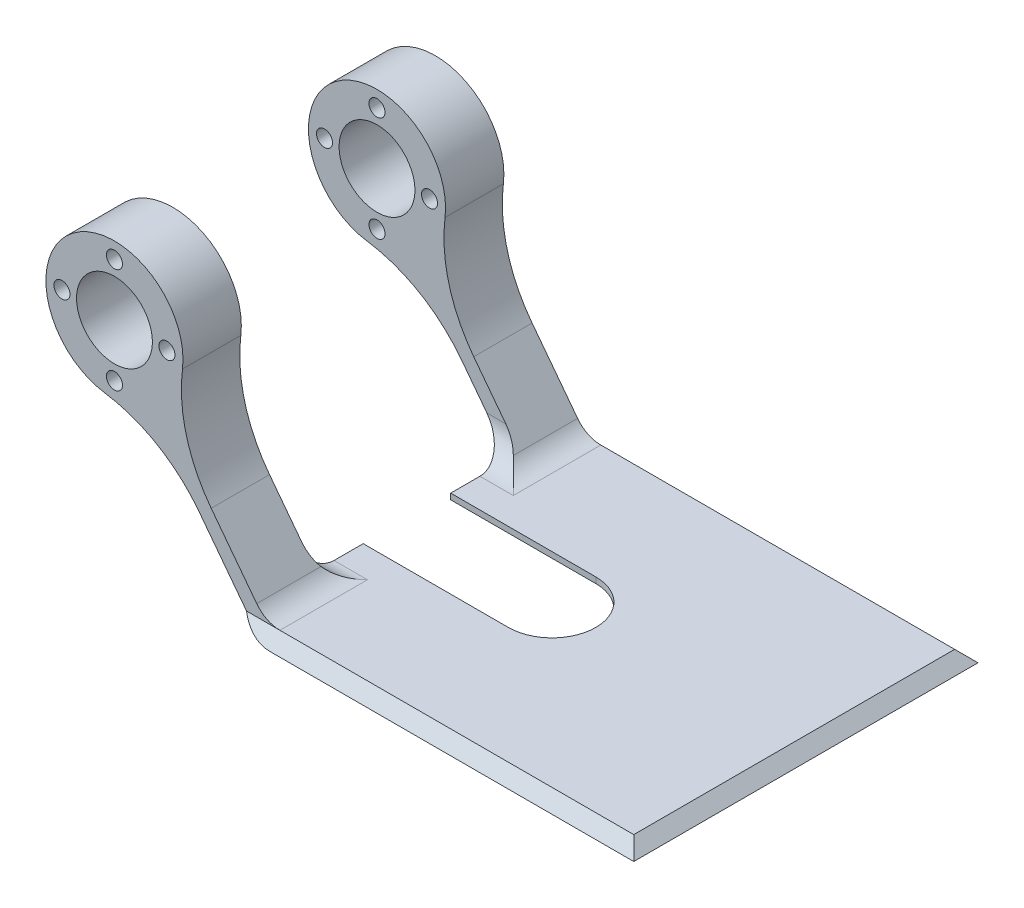
SolidWorks part; units mm, degrees
material "ABS"
ref_plane "Front Plane" through (0, 0, 0) normal (0, 0, 1) x (1, 0, 0)
ref_plane "Top Plane" through (0, 0, 0) normal (0, 1, 0) x (1, 0, 0)
ref_plane "Right Plane" through (0, 0, 0) normal (1, 0, 0) x (0, 0, -1)
sketch "Sketch1" plane through (0, 0, 0) normal (0, 1, 0) x (1, 0, 0)
  line L4 (-71.78, 65.2073) -> (70.97, 65.2073)
  line L5 (70.97, 65.2073) -> (70.97, -64.7927)
  line L6 (70.97, -64.7927) -> (-71.78, -64.7927)
  line L8 (-71.78, 65.2073) -> (-71.78, -64.7927)
  line L9 (-71.78, 65.2073) -> (70.97, -64.7927) construction
  line L10 (-71.78, -64.7927) -> (70.97, 65.2073) construction
  point P0 (-0.405, 0.2073)
  point P3 (-71.78, 0.2073)
  dimension "D1" = 142.75
  dimension "D2" = 130
extrude "Boss-Extrude1" add sketch "Sketch1" along normal blind 4
sketch "Sketch5" plane through (0, 4, 0) normal (0, 1, 0) x (1, 0, 0)
  line L1 (-116.78, 0.2073) -> (70.97, 0.2073) construction
  line L3 (70.97, -64.7927) -> (70.97, 65.2073) construction
ref_plane "Plane1" through (0, 0, -0.2073) normal (0, 0, 1) x (1, 0, 0)
chamfer "Chamfer4" distance 10 angle 45 2 edges at (-0.405, 4, -65.2073) (-0.405, 4, 64.7927)
chamfer "Chamfer5" distance 10 angle 45 1 edges at (70.97, 4, -0.2073)
ref_plane "Plane2" through (0, 0, 54.7927) normal (0, 0, -1) x (-1, 0, 0)
sketch "Sketch11" plane through (0, 0, 54.7927) normal (0, 0, -1) x (-1, 0, 0)
  line L0 (65.28, 4) -> (71.78, 4)
  line L1 (71.78, 4) -> (110.6251, 55.0273)
  line L2 (110.6251, 55.0273) -> (106.51, 58.16)
  line L3 (65.28, 4) -> (106.51, 58.16)
  line L4 (68.53, 4) -> (117.0476, 67.7331) construction
  line L5 (-60.97, 4) -> (71.78, 4) construction
  line L6 (117.0476, 67.7331) -> (99.0476, 67.7331) construction
  line L7 (117.0476, 67.7331) -> (135.0476, 67.7331) construction
  line L8 (117.0476, 67.7331) -> (117.0476, 85.7331) construction
  line L9 (117.0476, 67.7331) -> (117.0476, 49.7331) construction
  circle A0 centre (117.0476, 67.7331) radius 23.5
  circle A1 centre (99.0476, 67.7331) radius 2.75
  circle A2 centre (117.0476, 85.7331) radius 2.75
  circle A3 centre (135.0476, 67.7331) radius 2.75
  circle A4 centre (117.0476, 49.7331) radius 2.75
  circle A5 centre (117.0476, 67.7331) radius 13
  point P2 (108.5676, 56.5936)
  point P5 (54.3617, 2.4522)
  point P7 (54.3617, 2.4522)
  point P20 (71.78, 4)
  dimension "D6" = 5.5
  dimension "D9" = 26
  dimension "D10" = 47
  dimension "D1" = 6.5
  dimension "D2" = 54.16
  dimension "D3" = 41.23
  dimension "D4" = 18
  dimension "D5" = 18
  dimension "D7" = 18
  dimension "D8" = 18
  dimension "D11" = 14
extrude "Boss-Extrude3" add sketch "Sketch11" along normal blind 20 contours L4 L0 L1 A0 | L0 L4 A0 L3 | L1 A0 L3 L2 A5 A4 A3 A2 A1 | L4 A0 L1 L2 | A0 L4 L2 L3 region at (-84.3511, 26.9304, 54.7927) region at (-87.0055, 26.1466, 54.7927) region at (-108.0515, 88.7217, 54.7927) region at (-104.6785, 53.6142, 54.7927) region at (-106.7309, 52.0518, 54.7927)
sketch "Sketch12" plane through (0, 4, 0) normal (0, 1, 0) x (1, 0, 0)
  line L0 (60.97, -54.7927) -> (60.97, 55.2073) construction
  line L2 (-71.78, 55.2073) -> (-71.78, -34.7927) construction
  line L8 (-62.0334, -22.2927) -> (12.9666, -22.2927)
  line L9 (22.9666, -12.2927) -> (22.9666, 22.7073)
  line L10 (22.9666, 22.7073) -> (-62.0334, 22.7073)
  line L11 (-71.78, 15.2073) -> (-71.78, -14.7927)
  line L12 (60.97, 55.2073) -> (-71.78, 55.2073) construction
  line L13 (-65.28, -54.7927) -> (60.97, -54.7927) construction
  arc A4 (-71.495, -15.5295) -> (-71.78, -14.7927) centre (-80.988, -18.7771) ccw
  arc A5 (-71.495, -15.5295) -> (-62.0334, -22.2927) centre (-62.0334, -12.2927) ccw
  arc A6 (12.9666, -22.2927) -> (22.9666, -12.2927) centre (12.9666, -12.2927) ccw
  arc A7 (-62.0334, 22.7073) -> (-71.495, 15.9441) centre (-62.0334, 12.7073) ccw
  arc A8 (-71.78, 15.2073) -> (-71.495, 15.9441) centre (-80.988, 19.1917) ccw
  point P0 (60.97, 0.2073)
  point P4 (-92.6479, 18.3147)
  point P5 (-71.78, 0.2073)
  point P6 (-71.78, 36.534)
  point P23 (-71.78, 0.2073)
  dimension "D1" = 32.5
  dimension "D2" = 32.5
extrude "Cut-Extrude3" cut sketch "Sketch12" against normal up to next
fillet "Fillet5" radius 20 2 edges at (-71.78, 0, -37.2073) (-71.78, 0, 36.7927)
mirror "Mirror3" about plane through (0, 0, -0.2073) normal (0, 0, 1) of "Boss-Extrude3"
fillet "Fillet8" radius 10 4 edges at (-68.53, 4, -35.2073) (-68.53, 4, 34.7927) (-65.28, 4, -45.2073) (-65.28, 4, 44.7927)
fillet "Fillet9" radius 50 4 edges at (-104.9572, 47.5819, -45.2073) (-104.9572, 47.5819, 44.7927) (-100.8421, 50.7146, -45.2073) (-100.8421, 50.7146, 44.7927)
sketch "Sketch14" plane through (0, 4, 0) normal (0, 1, 0) x (1, 0, 0)
  line L0 (-71.78, 15.2073) -> (-22.0334, 15.2073)
  line L1 (-22.0334, -14.7927) -> (-71.78, -14.7927)
  line L2 (-62.0334, -22.2927) -> (12.9666, -22.2927)
  line L3 (22.9666, -12.2927) -> (22.9666, 22.7073)
  line L4 (22.9666, 22.7073) -> (-62.0334, 22.7073)
  arc A0 (-22.0334, -14.7927) -> (-22.0334, 15.2073) centre (-22.0334, 0.2073) ccw
  arc A1 (-71.495, -15.5295) -> (-71.78, -14.7927) centre (-80.988, -18.7771) ccw
  arc A2 (-71.495, -15.5295) -> (-62.0334, -22.2927) centre (-62.0334, -12.2927) ccw
  arc A3 (12.9666, -22.2927) -> (22.9666, -12.2927) centre (12.9666, -12.2927) ccw
  arc A4 (-62.0334, 22.7073) -> (-71.495, 15.9441) centre (-62.0334, 12.7073) ccw
  arc A5 (-71.78, 15.2073) -> (-71.495, 15.9441) centre (-80.988, 19.1917) ccw
  point P18 (22.9666, 22.7073)
extrude "Boss-Extrude5" add sketch "Sketch14" against normal blind 2
ref_plane "Plane3" through (0, 0, -0.2073) normal (0, 0, -1) x (-1, 0, 0)
